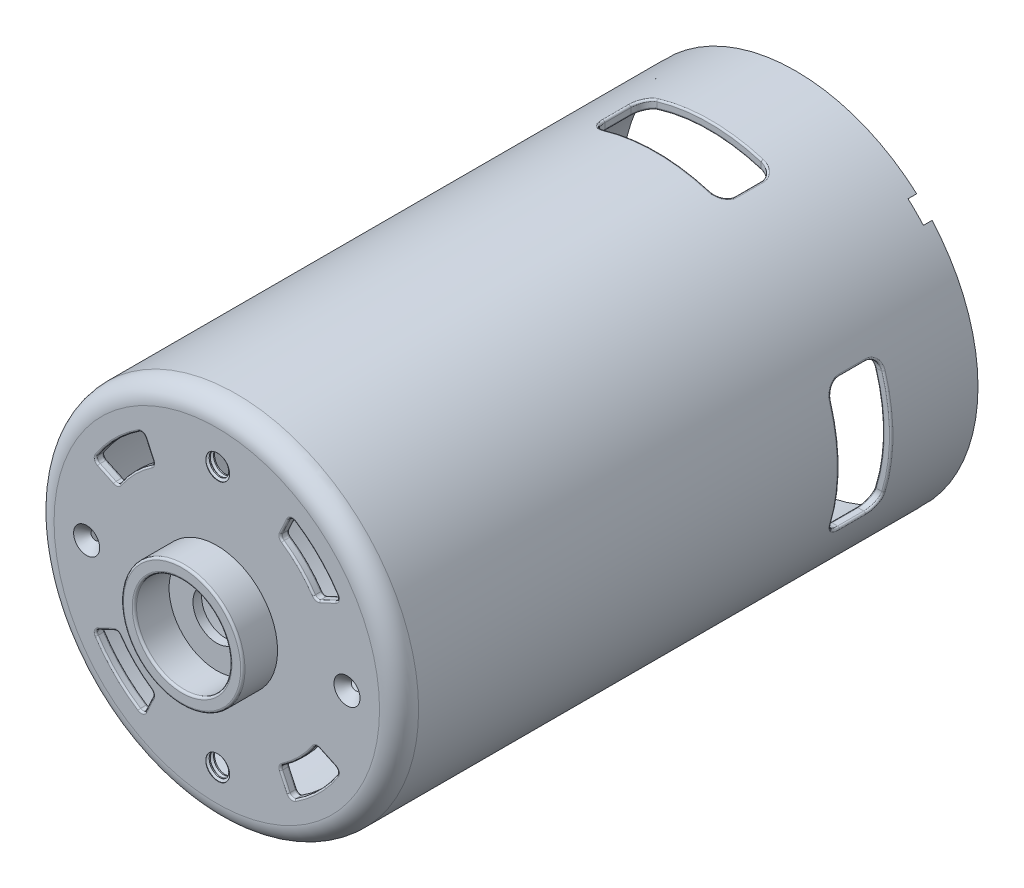
SolidWorks part; units mm, degrees
ref_plane "Front Plane" through (0, 0, 0) normal (0, 0, 1) x (1, 0, 0)
ref_plane "Top Plane" through (0, 0, 0) normal (0, 1, 0) x (1, 0, 0)
ref_plane "Right Plane" through (0, 0, 0) normal (1, 0, 0) x (0, 0, -1)
sketch "Sketch1" plane through (0, 0, 0) normal (0, 0, 1) x (1, 0, 0)
  circle A0 centre (0, 0) radius 21
  dimension "D1" = 42
extrude "Shell" add sketch "Sketch1" along normal mid plane 66.7
fillet "Fillet1" radius 2.25 1 edges at (21, 0, 33.35)
shell "Shell1" thickness 1
sketch "Sketch2" plane through (0, 0, 0) normal (0, 1, 0) x (1, 0, 0)
  line L1 (-6, 23.35) -> (6, 23.35)
  line L2 (-7.5, 21.85) -> (-7.5, 18.85)
  line L3 (-6, 17.35) -> (6, 17.35)
  line L4 (7.5, 21.85) -> (7.5, 18.85)
  arc A0 (6, 23.35) -> (7.5, 21.85) centre (6, 21.85) cw
  arc A1 (6, 17.35) -> (7.5, 18.85) centre (6, 18.85) ccw
  arc A2 (-7.5, 18.85) -> (-6, 17.35) centre (-6, 18.85) ccw
  arc A3 (-6, 23.35) -> (-7.5, 21.85) centre (-6, 21.85) ccw
  point P4 (0, 17.35)
  point P10 (7.5, 23.35)
  point P13 (7.5, 17.35)
  point P16 (-7.5, 17.35)
  dimension "D4" = 1.5
  dimension "D1" = 15
  dimension "D2" = 6
  dimension "D3" = 10
extrude "Cut-Extrude1" cut sketch "Sketch2" against normal up to surface (20.1246 mm away)
pattern_circular "CirPattern1" count 4 over 360 about axis through (0, 0, 0) along (0, 0, 1) of "Cut-Extrude1"
sketch "Sketch3" plane through (0, 0, 33.35) normal (0, 0, 1) x (1, 0, 0)
  point P0 (0, 15)
  point P1 (0, -15)
  dimension "D1" = 15
  dimension "D2" = 15
hole_wizard "Tap Drill for M3 Tap1" positions "Sketch7" profile "Sketch8" hole size "M3" standard "ISO"
sketch "Sketch7" plane through (0, 0, 33.35) normal (0, 0, 1) x (1, 0, 0)
  point P0 (0, 15)
  point P3 (0, -15)
sketch "Sketch8" plane through (0, 15, 33.35) normal (1, 0, 0) x (0, -1, 0)
  line L0 (0, 0) -> (0, 1.7501)
  line L1 (0, 1.7501) -> (1.25, 0.999)
  line L2 (1.25, 0.999) -> (1.25, 0)
  line L5 (1.25, 0) -> (0, 0)
  line L10 (0, 1.7501) -> (-1.25, 0.999) construction
  line L11 (0, -6.35) -> (0, 107.95) construction
  dimension "Hole Dia." = 2.5
  dimension "Hole Depth" = 0.999
  dimension "Drill Angle" = 118
thread "Thread3" pitch 0.5 start angle 0, offset 1, length 2, pitch 0.5, diameter 2.5
ref_plane "Plane4" through (-1.25, -15, 34.35) normal (0, -1, 0) x (-1, 0, 0)
sketch "Thread Profile4" plane through (-1.25, -15, 34.35) normal (0, -1, 0) x (-1, 0, 0)
  line L0 (0, 0) -> (0, 0.5) construction
  line L1 (0, 0) -> (0.2706, 0.1562)
  line L2 (0.2706, 0.1562) -> (0.2706, 0.2187)
  line L3 (0.2706, 0.2187) -> (0, 0.375)
  line L4 (0.2706, 0.1875) -> (0, 0.1875) construction
  line L11 (0, 0) -> (0, 0.375)
  point P2 (0, 0)
  dimension "Pitch" = 0.5
  dimension "Profile_Angle" = 60
  dimension "Profile_Land" = 0.0625
  dimension "Profile_Height" = 0.2706
thread "Thread4" pitch 0.5 profile "Thread Profile5" start angle 0, offset 1, length 2, pitch 0.5, diameter 2.5
ref_plane "Plane5" through (-1.25, 15, 34.35) normal (0, -1, 0) x (-1, 0, 0)
sketch "Thread Profile5" plane through (-1.25, 15, 34.35) normal (0, -1, 0) x (-1, 0, 0)
  line L0 (0, 0) -> (0, 0.5) construction
  line L1 (0, 0) -> (0.2706, 0.1562)
  line L2 (0.2706, 0.1562) -> (0.2706, 0.2187)
  line L3 (0.2706, 0.2187) -> (0, 0.375)
  line L4 (0.2706, 0.1875) -> (0, 0.1875) construction
  line L11 (0, 0) -> (0, 0.375)
  point P2 (0, 0)
  dimension "Pitch" = 0.5
  dimension "Profile_Angle" = 60
  dimension "Profile_Land" = 0.0625
  dimension "Profile_Height" = 0.2706
sketch "Sketch30" plane through (0, 0, -33.35) normal (0, 0, -1) x (-1, 0, 0)
  line L0 (-15.7331, 13.9654) -> (-14.9984, 13.2306)
  line L1 (-15.7331, 13.9654) -> (-13.9654, 15.7331)
  line L2 (-14.9984, 13.2306) -> (-13.2306, 14.9984)
  line L3 (-13.9654, 15.7331) -> (-13.2306, 14.9984)
  line L4 (-15.7331, 13.9654) -> (-13.2306, 14.9984) construction
  line L5 (-14.9984, 13.2306) -> (-13.9654, 15.7331) construction
  line L6 (0, 0) -> (-14.1145, 14.1145) construction
  line L7 (0, 0) -> (0, 21) construction
  line L8 (-14.8492, 14.8492) -> (-14.1145, 14.1145) construction
  circle A0 centre (0, 0) radius 21 construction
  circle A2 centre (0, 0) radius 21 construction
  circle A4 centre (0, 0) radius 20 construction
  point P1 (-14.4819, 14.4819)
  dimension "D1" = 45
  dimension "D2" = 2.5
extrude "Cut-Extrude3" cut sketch "Sketch30" against normal blind 1
pattern_circular "CirPattern4" count 4 over 360 about axis through (0, 0, 0) along (0, 0, 1) of "Cut-Extrude3"
sketch "Sketch31" plane through (0, 0, 33.35) normal (0, 0, 1) x (1, 0, 0)
  circle A0 centre (0, 0) radius 5.5
  circle A1 centre (0, 0) radius 7
  dimension "D1" = 1.5
  dimension "D2" = 11
extrude "Boss-Extrude2" add sketch "Sketch31" along normal blind 4
fillet "Fillet2" radius 0.25 2 edges at (7, 0, 37.35) (5.5, 0, 37.35)
sketch "Sketch32" plane through (0, 0, 33.35) normal (0, 0, 1) x (1, 0, 0)
  circle A0 centre (0, 0) radius 2.75
  dimension "D1" = 5.5
extrude "Shaft Hole" cut sketch "Sketch32" against normal up to surface (1 mm away) up to face at (0.1505, -15.0758, 32.35)
sketch "Sketch33" plane through (0, 0, 33.35) normal (0, 0, 1) x (1, 0, 0)
  line L0 (0, 0) -> (-11.6673, 11.6673) construction
  line L1 (0, 0) -> (0, 15) construction
  line L2 (-8.2521, 13.6358) -> (-7.3975, 11.803)
  line L3 (-13.6358, 8.2521) -> (-11.803, 7.3975)
  circle A0 centre (0, 0) radius 15 construction
  arc A1 (-13.844, 8.9773) -> (-8.9773, 13.844) centre (0, 0) cw
  arc A2 (-11.1777, 7.5703) -> (-7.5703, 11.1777) centre (0, 0) cw
  arc A3 (-7.5703, 11.1777) -> (-7.3975, 11.803) centre (-7.8506, 11.5917) ccw
  arc A4 (-11.1777, 7.5703) -> (-11.803, 7.3975) centre (-11.5917, 7.8506) cw
  arc A5 (-13.844, 8.9773) -> (-13.6358, 8.2521) centre (-13.4245, 8.7053) ccw
  arc A6 (-8.9773, 13.844) -> (-8.2521, 13.6358) centre (-8.7053, 13.4245) cw
  point P14 (-9.5459, 9.5459)
  point P21 (-14.1477, 8.4908)
  point P24 (-8.4908, 14.1477)
  dimension "D1" = 1.5
  dimension "D2" = 8
  dimension "D4" = 13.5
  dimension "D6" = 0.5
  dimension "D3" = 45
  dimension "D5" = 20
extrude "Cut-Extrude5" cut sketch "Sketch33" against normal up to surface (1 mm away) up to face at (2.75, 0, 32.35)
pattern_circular "CirPattern5" count 4 over 360 about axis through (0, 0, 0) along (0, 0, 1) of "Cut-Extrude5"
sketch "Sketch35" plane through (0, 0, 33.35) normal (0, 0, 1) x (1, 0, 0)
  circle A0 centre (15, 0) radius 1.5
  circle A1 centre (-15, 0) radius 1.5
  dimension "D1" = 3
  dimension "D2" = 15
  dimension "D3" = 30
extrude "Cut-Extrude6" cut sketch "Sketch35" against normal up to surface (1 mm away) draft 45
fillet "Fillet3" radius 0.2 128 edges at (-6.973, -19.8085, -17.7084) (0, -21, -17.35) (7.2051, -19.7253, -17.9568) (7.5, -19.615, -20.35) (6.973, -19.8085, -22.9916) (0, -21, -23.35) (-7.2051, -19.7253, -22.7432) (-6.977, -18.7436, -22.9882) (0, -20, -23.35) (7.2085, -18.6558, -22.7386) (7.5, -18.5405, -20.35) (6.977, -18.7436, -17.7118) (0, -20, -17.35) (-7.2085, -18.6558, -17.9614) (-19.7253, -7.2051, -17.9568) (19.8085, -6.973, -17.7084) (-19.615, -7.5, -20.35) (19.615, -7.5, -20.35) (-19.8085, -6.973, -22.9916) (19.7253, -7.2051, -22.7432) (-21, 0, -23.35) (-19.7253, 7.2051, -22.7432) (-19.615, 7.5, -20.35) (-19.8085, 6.973, -17.7084) (-18.6558, 7.2085, -17.9614) (-18.5405, 7.5, -20.35) (-19.3795, 4.9434, -20.7853) (-20, 0, -23.35) (-18.6261, -7.2847, -22.6242) (18.7108, -7.0643, -22.907) (-18.5405, -7.5, -20.35) (18.5405, -7.5, -20.35) (-18.7108, -7.0643, -17.793) (18.6261, -7.2847, -18.0758) (18.6261, 7.2847, -22.6242) (18.5405, 7.5, -20.35) (18.7108, 7.0643, -17.793) (20, 0, -17.35) (21, 0, -17.35) (19.7253, 7.2051, -17.9568) (19.615, 7.5, -20.35) (19.8085, 6.973, -22.9916) (-7.5, 18.5405, -20.35) (-6.8233, 18.8001, -17.5961) (0, 20, -17.35) (7.3348, 18.6065, -18.1657) (7.5, 18.5405, -20.35) (6.977, 18.7436, -22.9882) (0, 20, -23.35) (0, 21, -23.35) (7.2051, 19.7253, -22.7432) (7.5, 19.615, -20.35) (6.973, 19.8085, -17.7084) (0, 21, -17.35) (-7.2051, 19.7253, -17.9568) (-7.5, 19.615, -20.35) (7.3687, -11.4585, 33.35) (9.5459, -9.5459, 33.35) (11.4585, -7.3687, 33.35) (12.7194, -7.8248, 33.35) (13.9051, -8.5673, 33.35) (11.6673, -11.6673, 33.35) (8.5673, -13.9051, 33.35) (8.5673, -13.9051, 32.35) (11.6673, -11.6673, 32.35) (13.9051, -8.5673, 32.35) (12.7194, -7.8248, 32.35) (11.4585, -7.3687, 32.35) (9.5459, -9.5459, 32.35) (7.3687, -11.4585, 32.35) (-8.5673, -13.9051, 32.35) (-7.8248, -12.7194, 32.35) (-7.3687, -11.4585, 32.35) (-9.5459, -9.5459, 32.35) (-11.4585, -7.3687, 32.35) (-12.7194, -7.8248, 32.35) (-13.9051, -8.5673, 32.35) (-13.9051, -8.5673, 33.35) (-12.7194, -7.8248, 33.35) (-11.4585, -7.3687, 33.35) (-9.5459, -9.5459, 33.35) (-7.3687, -11.4585, 33.35) (-7.8248, -12.7194, 33.35) (-8.5673, -13.9051, 33.35) (7.3687, 11.4585, 33.35) (7.8248, 12.7194, 33.35) (8.5673, 13.9051, 33.35) (11.6673, 11.6673, 33.35) (13.9051, 8.5673, 33.35) (12.7194, 7.8248, 33.35) (11.4585, 7.3687, 33.35) (11.4585, 7.3687, 32.35) (12.7194, 7.8248, 32.35) (13.9051, 8.5673, 32.35) (11.6673, 11.6673, 32.35) (8.5673, 13.9051, 32.35) (7.8248, 12.7194, 32.35) (7.3687, 11.4585, 32.35) (-12.7194, 7.8248, 32.35) (-11.4585, 7.3687, 32.35) (-9.5459, 9.5459, 32.35) (-7.3687, 11.4585, 32.35) (-7.8248, 12.7194, 32.35) (-8.5673, 13.9051, 32.35) (-11.6673, 11.6673, 32.35) (-8.5673, 13.9051, 33.35) (-7.8248, 12.7194, 33.35) (-7.3687, 11.4585, 33.35) (-9.5459, 9.5459, 33.35) (-11.4585, 7.3687, 33.35) (-12.7194, 7.8248, 33.35) (-13.9051, 8.5673, 33.35) (-7.5, -19.615, -20.35) (-7.5, -18.5405, -20.35) (-21, 0, -17.35) (-20, 0, -17.35) (20, 0, -23.35) (21, 0, -23.35) (-4.95, 19.3778, -20.7788) (-6.973, 19.8085, -22.9916) (7.8248, -12.7194, 33.35) (7.8248, -12.7194, 32.35) (-11.6673, -11.6673, 32.35) (-11.6673, -11.6673, 33.35) (9.5459, 9.5459, 33.35) (9.5459, 9.5459, 32.35) (-13.9051, 8.5673, 32.35) (-11.6673, 11.6673, 33.35)
